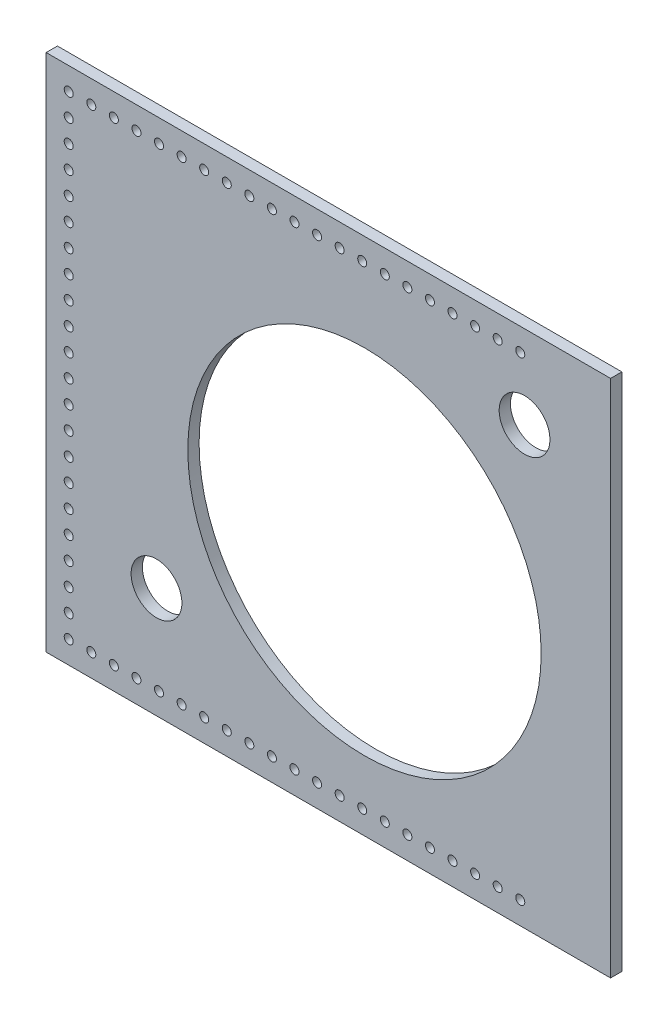
SolidWorks part; units mm, degrees
material "6061 Alloy"
ref_plane "Front Plane" through (0, 0, 0) normal (0, 0, 1) x (1, 0, 0)
ref_plane "Top Plane" through (0, 0, 0) normal (0, 1, 0) x (1, 0, 0)
ref_plane "Right Plane" through (0, 0, 0) normal (1, 0, 0) x (0, 0, -1)
sketch "Sketch1" plane through (0, 0, 0) normal (0, 0, 1) x (1, 0, 0)
  line L1 (0, 0) -> (317.5, 0)
  line L2 (0, 0) -> (0, 292.1)
  line L4 (317.5, 0) -> (317.5, 292.1)
  line L5 (0, 292.1) -> (317.5, 292.1)
  circle A0 centre (179.07, 138.43) radius 99.3775
  circle A1 centre (12.7, 279.4) radius 2.54
  circle A2 centre (25.4, 279.4) radius 2.54
  circle A3 centre (38.1, 279.4) radius 2.54
  circle A4 centre (50.8, 279.4) radius 2.54
  circle A5 centre (63.5, 279.4) radius 2.54
  circle A6 centre (76.2, 279.4) radius 2.54
  circle A7 centre (88.9, 279.4) radius 2.54
  circle A8 centre (101.6, 279.4) radius 2.54
  circle A9 centre (114.3, 279.4) radius 2.54
  circle A10 centre (127, 279.4) radius 2.54
  circle A11 centre (139.7, 279.4) radius 2.54
  circle A12 centre (152.4, 279.4) radius 2.54
  circle A13 centre (165.1, 279.4) radius 2.54
  circle A14 centre (177.8, 279.4) radius 2.54
  circle A15 centre (190.5, 279.4) radius 2.54
  circle A16 centre (203.2, 279.4) radius 2.54
  circle A17 centre (215.9, 279.4) radius 2.54
  circle A18 centre (228.6, 279.4) radius 2.54
  circle A19 centre (241.3, 279.4) radius 2.54
  circle A20 centre (254, 279.4) radius 2.54
  circle A21 centre (266.7, 279.4) radius 2.54
  circle A24 centre (12.7, 266.7) radius 2.54
  circle A25 centre (12.7, 254) radius 2.54
  circle A26 centre (12.7, 241.3) radius 2.54
  circle A27 centre (12.7, 228.6) radius 2.54
  circle A28 centre (12.7, 215.9) radius 2.54
  circle A29 centre (12.7, 203.2) radius 2.54
  circle A30 centre (12.7, 190.5) radius 2.54
  circle A31 centre (12.7, 177.8) radius 2.54
  circle A32 centre (12.7, 165.1) radius 2.54
  circle A33 centre (12.7, 152.4) radius 2.54
  circle A34 centre (12.7, 139.7) radius 2.54
  circle A35 centre (12.7, 127) radius 2.54
  circle A36 centre (12.7, 114.3) radius 2.54
  circle A37 centre (12.7, 101.6) radius 2.54
  circle A38 centre (12.7, 88.9) radius 2.54
  circle A39 centre (12.7, 76.2) radius 2.54
  circle A40 centre (12.7, 63.5) radius 2.54
  circle A41 centre (12.7, 50.8) radius 2.54
  circle A42 centre (12.7, 38.1) radius 2.54
  circle A43 centre (12.7, 25.4) radius 2.54
  circle A44 centre (12.7, 12.7) radius 2.54
  circle A45 centre (25.4, 12.7) radius 2.54
  circle A46 centre (38.1, 12.7) radius 2.54
  circle A47 centre (50.8, 12.7) radius 2.54
  circle A48 centre (63.5, 12.7) radius 2.54
  circle A49 centre (76.2, 12.7) radius 2.54
  circle A50 centre (88.9, 12.7) radius 2.54
  circle A51 centre (101.6, 12.7) radius 2.54
  circle A52 centre (114.3, 12.7) radius 2.54
  circle A53 centre (127, 12.7) radius 2.54
  circle A54 centre (139.7, 12.7) radius 2.54
  circle A55 centre (152.4, 12.7) radius 2.54
  circle A56 centre (165.1, 12.7) radius 2.54
  circle A57 centre (177.8, 12.7) radius 2.54
  circle A58 centre (190.5, 12.7) radius 2.54
  circle A59 centre (203.2, 12.7) radius 2.54
  circle A60 centre (215.9, 12.7) radius 2.54
  circle A61 centre (228.6, 12.7) radius 2.54
  circle A62 centre (241.3, 12.7) radius 2.54
  circle A63 centre (254, 12.7) radius 2.54
  circle A64 centre (266.7, 12.7) radius 2.54
  circle A66 centre (179.07, 138.43) radius 179.07 construction
  dimension "D3" = 198.755
  dimension "D4" = 5.08
  dimension "D5" = 12.7
  dimension "D11" = 12.7
  dimension "D12" = 266.7
  dimension "D14" = 292.1
  dimension "D15" = 358.14
  dimension "D2" = 138.43
  dimension "D6" = 12.7
  dimension "D7" = 317.5
  dimension "D8" = 21
  dimension "D9" = 22
  dimension "D10" = 21
  dimension "D13" = 138.43
extrude "Boss-Extrude1" add sketch "Sketch1" along normal blind 6.35
sketch "Sketch2" plane through (0, 0, 6.35) normal (0, 0, 1) x (1, 0, 0)
  line L0 (177.2452, 140.4926) -> (-32620.0354, 37211.0747) construction
  line L1 (62.0797, 62.0797) -> (0, 62.0797) construction
  line L2 (62.0797, 62.0797) -> (62.0797, 0) construction
  line L3 (62.0797, 0) -> (0, 0) construction
  line L4 (0, 62.0797) -> (0, 0) construction
  line L5 (317.5, 292.1) -> (0, 292.1) construction
  circle A0 centre (62.0797, 62.0797) radius 14.2875
  circle A2 centre (179.07, 138.43) radius 127 construction
  circle A4 centre (62.0797, 62.0797) radius 12.7 construction
  circle A5 centre (269.1087, 245.2435) radius 14.2875
  dimension "D1" = 28.575
  dimension "D2" = 139.7
  dimension "D3" = 254
  dimension "D4" = 25.4
  dimension "D5" = 48.5
extrude "Cut-Extrude1" cut sketch "Sketch2" against normal through all
